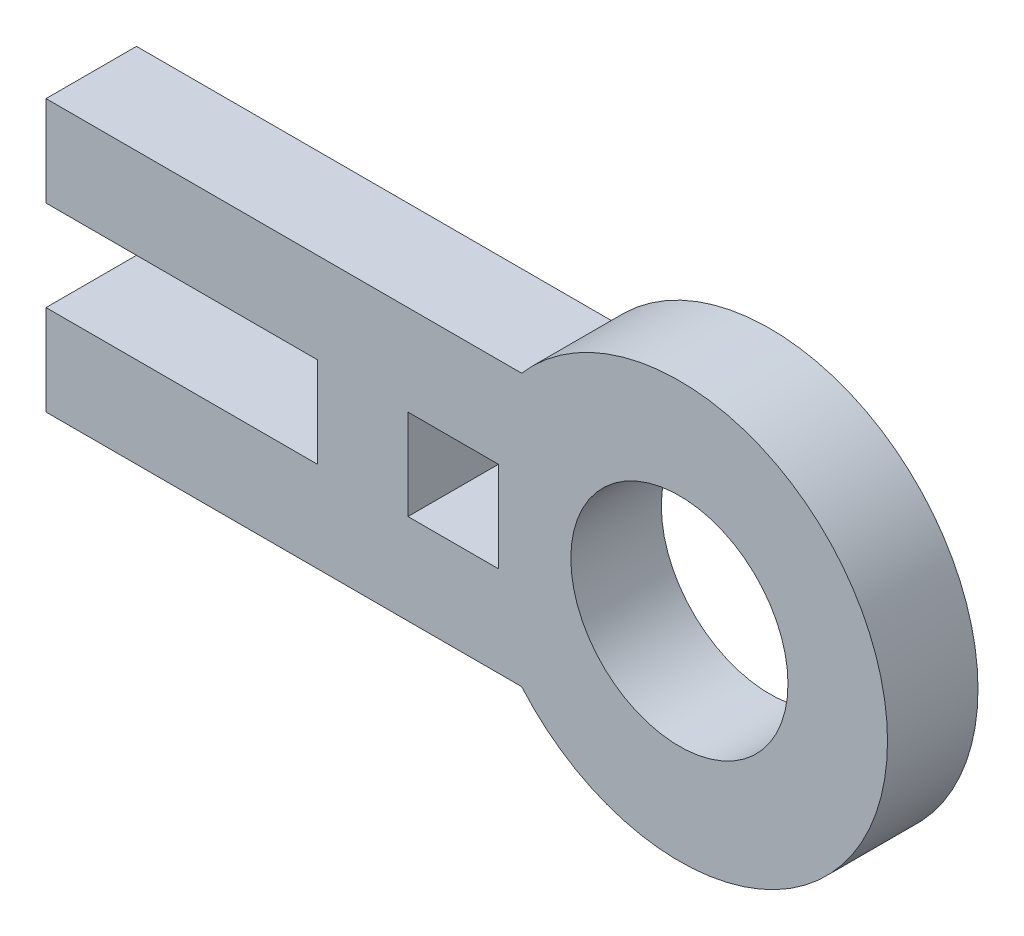
SolidWorks part; units mm, degrees
ref_plane "Front Plane" through (0, 0, 0) normal (0, 0, 1) x (1, 0, 0)
ref_plane "Top Plane" through (0, 0, 0) normal (0, 1, 0) x (1, 0, 0)
ref_plane "Right Plane" through (0, 0, 0) normal (1, 0, 0) x (0, 0, -1)
sketch "Sketch1" plane through (0, 0, 0) normal (0, 0, 1) x (1, 0, 0)
  line L0 (0, 0) -> (-28.0385, 0) construction
  line L1 (-11.225, -2.5) -> (-20, -2.5)
  line L2 (-20, -2.5) -> (-20, 2.5)
  line L3 (-20, 2.5) -> (-11.225, 2.5)
  line L4 (-8.7178, -7.5) -> (-35, -7.5)
  line L5 (-35, -7.5) -> (-35, 7.5)
  line L6 (-35, 7.5) -> (-8.7178, 7.5)
  line L7 (-20, 2.5) -> (-35, 2.5)
  line L8 (-20, -2.5) -> (-35, -2.5)
  circle A0 centre (0, 0) radius 6
  circle A1 centre (0, 0) radius 11.5
  point P7 (-20, 0)
  point P12 (-35, 0)
  dimension "D1" = 12
  dimension "D2" = 23
  dimension "D3" = 5
  dimension "D4" = 15
  dimension "D5" = 35
  dimension "D6" = 20
extrude "Boss-Extrude1" add sketch "Sketch1" along normal blind 5 contours A0 A1 | A1 L6 L5 L7 L3 | A1 L1 L8 L5 L4 | L0 A1 L3 L2 | A1 L0 L2 L1 region at (-11.1077, 1.222, 0) region at (-15.704, -1.2567, 0) region at (-15.704, 1.2567, 0) region at (-22.6043, 5.0415, 0) region at (-22.6043, -5.0415, 0)
sketch "Sketch2" plane through (0, 0, 5) normal (0, 0, 1) x (1, 0, 0)
  line L0 (-20, -2.5) -> (-10, -2.5)
  line L1 (-10, -2.5) -> (-10, 2.5)
  line L2 (-10, 2.5) -> (-20, 2.5)
  line L3 (-15, -2.5) -> (-15, 2.5)
  line L4 (-20, -2.5) -> (-20, 2.5) construction
  line L5 (-20, -2.5) -> (-20, 2.5)
  dimension "D1" = 5
  dimension "D2" = 5
extrude "Cut-Extrude1" cut sketch "Sketch2" against normal blind 5 contours L3 L0 L1 L2 region at (-12.5, 0, 5)
